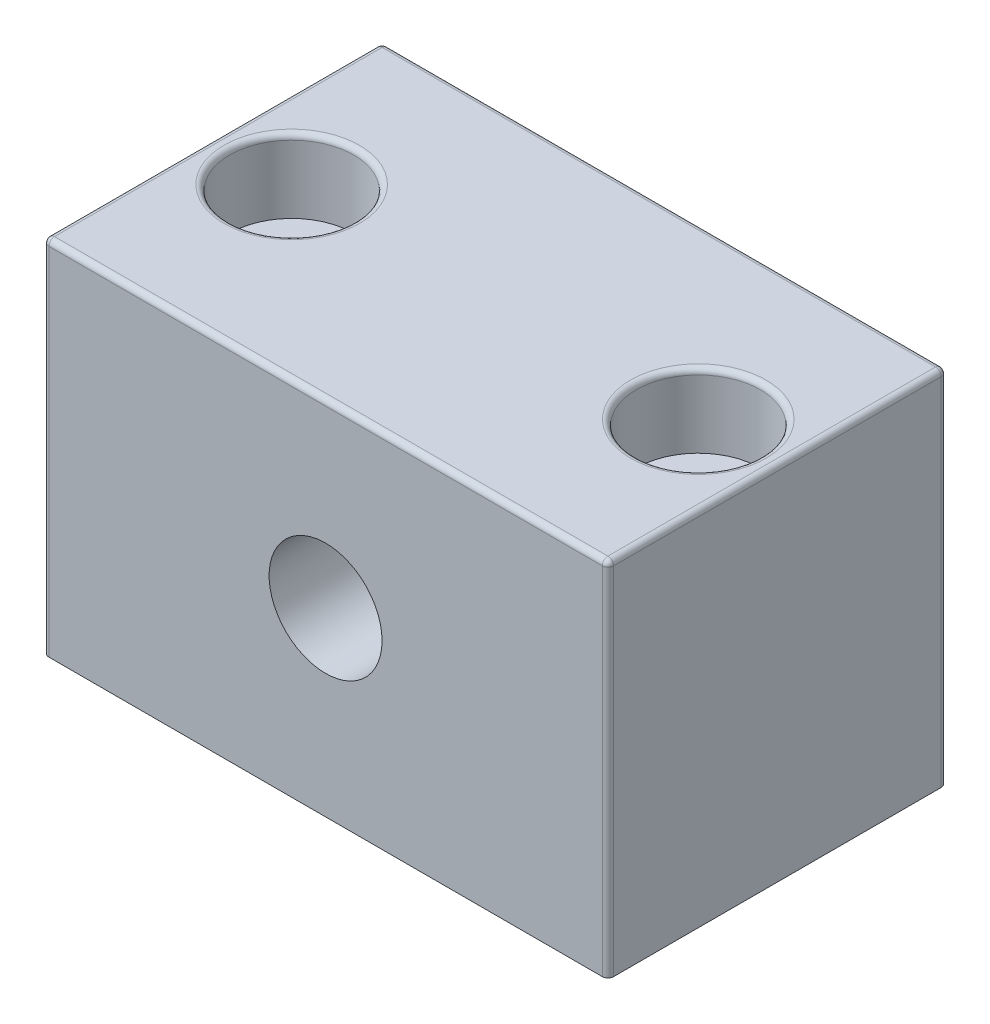
SolidWorks part; units mm, degrees
material "1060 Alloy"
ref_plane "Front Plane" through (0, 0, 0) normal (0, 0, 1) x (1, 0, 0)
ref_plane "Top Plane" through (0, 0, 0) normal (0, 1, 0) x (1, 0, 0)
ref_plane "Right Plane" through (0, 0, 0) normal (1, 0, 0) x (0, 0, -1)
sketch "Sketch1" plane through (0, 0, 0) normal (0, 0, 1) x (1, 0, 0)
  line L1 (0, 0) -> (50, 0)
  line L2 (0, 0) -> (0, 32)
  line L3 (0, 32) -> (50, 32)
  line L4 (50, 0) -> (50, 32)
  dimension "D1" = 32
  dimension "D2" = 50
extrude "Boss-Extrude1" add sketch "Sketch1" along normal blind 15 and the other way blind 15
sketch "Sketch2" plane through (0, 0, 15) normal (0, 0, 1) x (1, 0, 0)
  line L0 (25, 32) -> (25, 0) construction
  line L1 (50, 32) -> (0, 32) construction
  line L2 (0, 0) -> (50, 0) construction
  circle A0 centre (25, 16) radius 5
  point P8 (25, 16)
  dimension "D1" = 10
extrude "Cut-Extrude1" cut sketch "Sketch2" against normal through all
sketch "Sketch3" plane through (0, 32, 0) normal (0, 1, 0) x (1, 0, 0)
  line L0 (25, 15) -> (25, -15) construction
  line L1 (50, 15) -> (0, 15) construction
  line L2 (50, -15) -> (0, -15) construction
  circle A0 centre (43, 0) radius 5.5
  dimension "D1" = 18
  dimension "D2" = 11
extrude "Cut-Extrude2" cut sketch "Sketch3" against normal blind 6.5
sketch "Sketch4" plane through (0, 25.5, 0) normal (0, 1, 0) x (1, 0, 0)
  circle A0 centre (43, 0) radius 3.3
  dimension "D1" = 6.6
extrude "Cut-Extrude3" cut sketch "Sketch4" against normal through all
ref_plane "Plane1" through (25, 0, 0) normal (1, 0, 0) x (0, 0, -1)
mirror "Mirror1" about plane through (25, 0, 0) normal (1, 0, 0) of "Cut-Extrude2", "Cut-Extrude3"
fillet "Fillet1" radius 0.5 10 edges at (7, 32, 5.5) (43, 32, 5.5) (25, 32, -15) (50, 32, 0) (25, 32, 15) (0, 32, 0) (0, 16, -15) (50, 16, -15) (50, 16, 15) (0, 16, 15)
